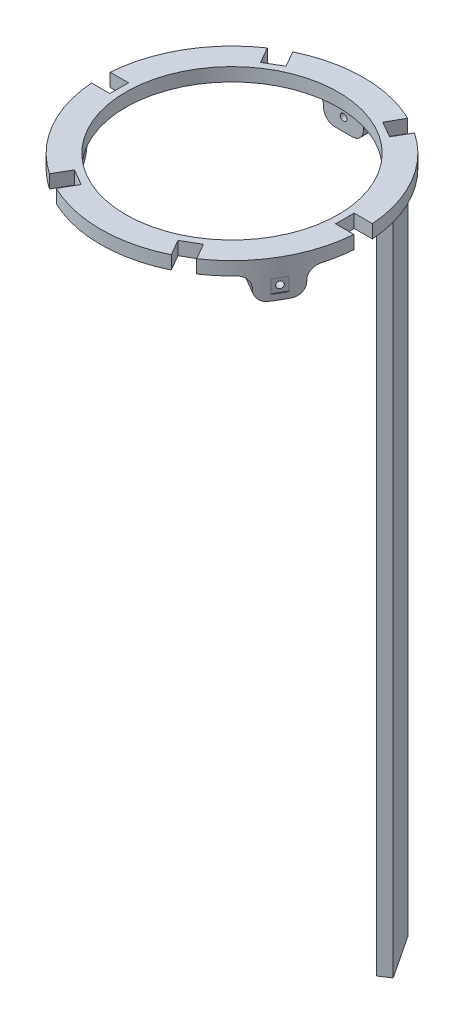
SolidWorks part; units mm, degrees
ref_plane "Спереди" through (0, 0, 0) normal (0, 0, 1) x (1, 0, 0)
ref_plane "Сверху" through (0, 0, 0) normal (0, 1, 0) x (1, 0, 0)
ref_plane "Справа" through (0, 0, 0) normal (1, 0, 0) x (0, 0, -1)
sketch "Эскиз1" plane through (0, 0, 0) normal (0, 1, 0) x (1, 0, 0)
  circle A0 centre (0, 0) radius 99
  dimension "D1" = 198
extrude "Бобышка-Вытянуть1" add sketch "Эскиз1" along normal blind 10
sketch "Эскиз2" plane through (0, 10, 0) normal (0, 1, 0) x (1, 0, 0)
  line L0 (-92, 0) -> (0, 0) construction
  line L1 (-99, 7) -> (-85, 7)
  line L2 (-99, 7) -> (-99, -7)
  line L3 (-99, -7) -> (-85, -7)
  line L4 (-85, 7) -> (-85, -7)
  line L5 (-99, 7) -> (-85, -7) construction
  line L6 (-99, -7) -> (-85, 7) construction
  circle A0 centre (0, 0) radius 99 construction
  point P0 (-92, 0)
  dimension "D1" = 14
  dimension "D2" = 14
extrude "Вырез-Вытянуть1" cut sketch "Эскиз2" against normal through all
pattern_circular "Круговой массив1" count 6 over 360 about axis through (0, 10, 0) along (0, 1, 0) of "Вырез-Вытянуть1"
sketch "Эскиз3" plane through (0, 10, 0) normal (0, 1, 0) x (1, 0, 0)
  line L1 (-85, -7) -> (-85, 7) construction
  circle A0 centre (0, 0) radius 80
  point P5 (-80, 0)
  dimension "D1" = 5
extrude "Вырез-Вытянуть2" cut sketch "Эскиз3" against normal through all
ref_plane "Плоскость1" through (0, 0, -99) normal (0, 0, -1) x (-1, 0, 0)
sketch "Эскиз6" plane through (0, 0, -99) normal (0, 0, -1) x (-1, 0, 0)
  line L0 (-43.3139, 0) -> (43.3139, 0) construction
  line L1 (-15, -17.9681) -> (15, -17.9681)
  line L2 (-15, -17.9681) -> (-15, 0)
  line L3 (-15, 0) -> (15, 0)
  line L4 (15, -17.9681) -> (15, 0)
  line L5 (-15, -17.9681) -> (15, 0) construction
  line L6 (-15, 0) -> (15, -17.9681) construction
  line L7 (0, -8.984) -> (0, 0) construction
  point P0 (0, -8.984)
  dimension "D1" = 30
extrude "Бобышка-Вытянуть2" add sketch "Эскиз6" against normal blind 15
sketch "Эскиз7" plane through (0, 10, 0) normal (0, 1, 0) x (1, 0, 0)
  circle A0 centre (0, 0) radius 99
  arc A1 (43.3139, 89.0219) -> (-43.3139, 89.0219) centre (0, 0) ccw construction
  circle A2 centre (0, 0) radius 104
  dimension "D1" = 5
extrude "Вырез-Вытянуть3" cut sketch "Эскиз7" against normal through all
sketch "Эскиз8" plane through (0, 0, -99) normal (0, 0, -1) x (-1, 0, 0)
  line L0 (0, -8.5) -> (0, 0) construction
  circle A0 centre (0, -8.5) radius 2.5
  dimension "D2" = 5
  dimension "D1" = 8.5
extrude "Вырез-Вытянуть4" cut sketch "Эскиз8" against normal up to next
fillet "Скругление1" radius 8.5 4 edges at (-15, 0, -90.9285) (15, 0, -90.9285) (-15, -17.9681, -90.9285) (15, -17.9681, -90.9285)
sketch "Эскиз9" plane through (0, 0, -99) normal (0, 0, -1) x (-1, 0, 0)
  line L1 (-5, -3.5) -> (5, -3.5)
  line L2 (-5, -3.5) -> (-5, -13.5)
  line L3 (-5, -13.5) -> (5, -13.5)
  line L4 (5, -3.5) -> (5, -13.5)
  line L5 (-5, -3.5) -> (5, -13.5) construction
  line L6 (-5, -13.5) -> (5, -3.5) construction
  point P0 (0, -8.5)
  dimension "D1" = 10
  dimension "D2" = 10
extrude "Вырез-Вытянуть5" cut sketch "Эскиз9" against normal blind 0.5
pattern_circular "Круговой массив3" count 3 over 360 about axis through (0, 0, 0) along (0, 1, 0) of "Бобышка-Вытянуть2", "Вырез-Вытянуть3", "Вырез-Вытянуть4", "Скругление1", "Вырез-Вытянуть5"
sketch "Эскиз10" plane through (0, 0, 0) normal (0, -1, 0) x (1, 0, 0)
  line L0 (67.0955, -65.2982) -> (88.5621, -32.8102)
  line L1 (88.5621, -32.8102) -> (81.0551, -27.8499)
  line L2 (81.0551, -27.8499) -> (59.5884, -60.3378)
  line L3 (59.5884, -60.3378) -> (67.0955, -65.2982)
extrude "Бобышка-Вытянуть3" add sketch "Эскиз10" along normal blind 500
